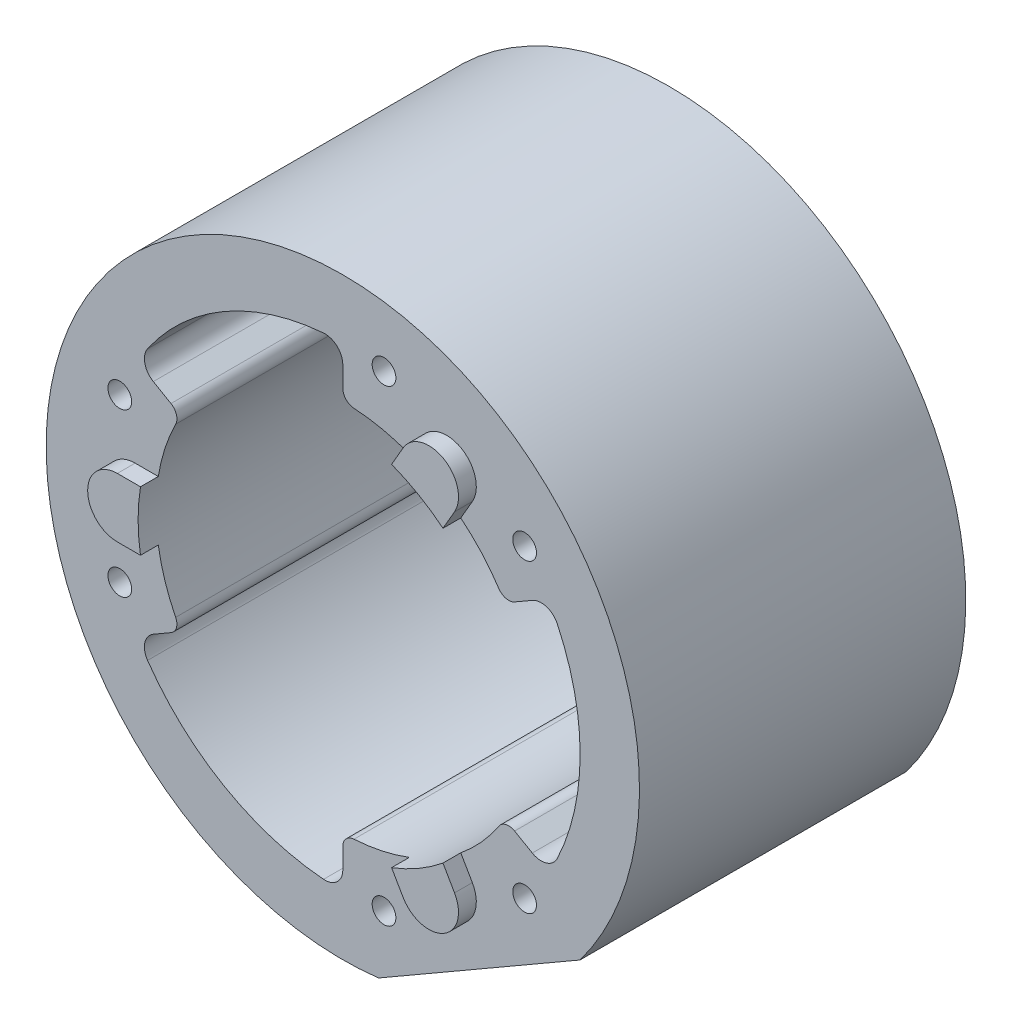
SolidWorks part; units mm, degrees
material "ABS"
ref_plane "Front Plane" through (0, 0, 0) normal (0, 0, 1) x (1, 0, 0)
ref_plane "Top Plane" through (0, 0, 0) normal (0, 1, 0) x (1, 0, 0)
ref_plane "Right Plane" through (0, 0, 0) normal (1, 0, 0) x (0, 0, -1)
sketch "Sketch1" plane through (0, 0, 0) normal (0, 0, 1) x (1, 0, 0)
  line L2 (-28.9601, 16.7201) -> (-31.9374, 18.4391)
  line L3 (0, 33.4402) -> (0, 36.8782)
  line L6 (28.9601, 16.7201) -> (31.9374, 18.4391)
  line L7 (28.9601, -16.7201) -> (31.9374, -18.4391)
  line L10 (0, -33.4402) -> (0, -36.8782)
  line L11 (-28.9601, -16.7201) -> (-31.9374, -18.4391)
  arc A0 (39.9706, -30.0392) -> (6.0294, -49.6351) centre (0, 0) ccw
  circle A1 centre (-37.5877, 13.6808) radius 2
  circle A2 centre (-37.5877, -13.6808) radius 2
  arc A3 (26.2908, 17.3506) -> (1.8806, 31.4438) centre (0, 0) ccw
  arc A4 (-28.1714, 14.0933) -> (-28.9601, 16.7201) centre (-29.9601, 14.9881) ccw
  arc A5 (-32.9053, 22.7429) -> (-31.9374, 18.4391) centre (-30.4374, 21.0372) ccw
  arc A6 (-3.2432, 39.8683) -> (-32.9053, 22.7429) centre (0, 0) ccw
  arc A7 (0, 36.8782) -> (-3.2432, 39.8683) centre (-3, 36.8782) ccw
  circle A8 centre (6.9459, 39.3923) radius 2
  arc A9 (1.8806, -31.4438) -> (26.2908, -17.3506) centre (0, 0) ccw
  circle A10 centre (30.6418, 25.7115) radius 2
  arc A11 (26.2908, 17.3506) -> (28.9601, 16.7201) centre (27.9601, 18.4522) ccw
  arc A12 (36.1486, 17.1254) -> (31.9374, 18.4391) centre (33.4374, 15.841) ccw
  arc A13 (36.1486, -17.1254) -> (36.1486, 17.1254) centre (0, 0) ccw
  arc A14 (31.9374, -18.4391) -> (36.1486, -17.1254) centre (33.4374, -15.841) ccw
  arc A15 (28.9601, -16.7201) -> (26.2908, -17.3506) centre (27.9601, -18.4522) ccw
  circle A16 centre (30.6418, -25.7115) radius 2
  circle A18 centre (6.9459, -39.3923) radius 2
  arc A19 (1.8806, -31.4438) -> (26.2908, -17.3506) centre (0, 0) ccw
  arc A20 (1.8806, -31.4438) -> (0, -33.4402) centre (2, -33.4402) ccw
  arc A21 (-3.2432, -39.8683) -> (0, -36.8782) centre (-3, -36.8782) ccw
  arc A22 (-32.9053, -22.7429) -> (-3.2432, -39.8683) centre (0, 0) ccw
  arc A23 (-31.9374, -18.4391) -> (-32.9053, -22.7429) centre (-30.4374, -21.0372) ccw
  arc A24 (-28.9601, -16.7201) -> (-28.1714, -14.0933) centre (-29.9601, -14.9881) ccw
  arc A26 (0, 33.4402) -> (1.8806, 31.4438) centre (2, 33.4402) ccw
  arc A27 (26.2908, 17.3506) -> (1.8806, 31.4438) centre (0, 0) ccw
  arc A28 (-28.1714, 14.0933) -> (-28.1714, -14.0933) centre (0, 0) ccw
  circle A30 centre (0, 0) radius 50
extrude "Boss-Extrude1" add sketch "Sketch1" along normal blind 55 contours A0 A30 A1 A2 A8 A10 A16 A18 A28 A4 L2 A5 A6 A7 L3 A26 A3 A11 L6 A12 A13 A14 L7 A15 A9 A20 L10 A21 A22 A23 L11 A24 region at (24.2929, -42.0765, 0)
sketch "Sketch2" plane through (0, 0, 55) normal (0, 0, 1) x (1, 0, 0)
  line L0 (-35, -5) -> (-31.1006, -5)
  line L1 (-35, 5) -> (-31.1006, 5)
  line L2 (21.8301, 27.8109) -> (19.8804, 24.4339)
  line L3 (13.1699, 32.8109) -> (11.2202, 29.4339)
  line L4 (21.8301, -27.8109) -> (19.8804, -24.4339)
  line L6 (13.1699, -32.8109) -> (11.2202, -29.4339)
  arc A0 (-35, 5) -> (-35, -5) centre (-35, 0) ccw
  arc A1 (21.8301, 27.8109) -> (13.1699, 32.8109) centre (17.5, 30.3109) ccw
  arc A2 (13.1699, -32.8109) -> (21.8301, -27.8109) centre (17.5, -30.3109) ccw
  arc A5 (-31.1006, 5) -> (-31.1006, -5) centre (0, 0) ccw
  arc A6 (11.2202, -29.4339) -> (19.8804, -24.4339) centre (0, 0) ccw
  arc A7 (19.8804, 24.4339) -> (11.2202, 29.4339) centre (0, 0) ccw
extrude "Boss-Extrude2" add sketch "Sketch2" along normal blind 3
sketch "Sketch3" plane through (0, 0, 55) normal (0, 0, 1) x (1, 0, 0)
  line L0 (6.0294, -49.6351) -> (39.9706, -30.0392)
  arc A1 (6.0294, -49.6351) -> (39.9706, -30.0392) centre (0, 0) ccw
extrude "Cut-Extrude1" cut sketch "Sketch3" against normal through all
sketch "Sketch4" plane through (23, -39.8372, 0) normal (0.5, -0.866, 0) x (0.866, 0.5, 0)
  line L0 (-19.5959, 27.5) -> (19.5959, 27.5) construction
  line L1 (-19.5959, 0) -> (-19.5959, 55) construction
  line L2 (19.5959, 0) -> (19.5959, 55) construction
  line L3 (0, 55) -> (0, 0) construction
  line L4 (19.5959, 55) -> (-19.5959, 55) construction
  circle A0 centre (0, 41.5) radius 2.6
  circle A1 centre (0, 13.5) radius 2.6
  dimension "D1" = 5.2
  dimension "D2" = 5.2
  dimension "D3" = 14
  dimension "D4" = 14
extrude "Cut-Extrude2" cut sketch "Sketch4" against normal up to next
extrude "Boss-Extrude3" add sketch "Sketch2<2>" along normal blind 3 and the other way blind 58
sketch "Sketch2<2>" plane through (0, 0, 55) normal (0, 0, 1) x (1, 0, 0) same geometry as "Sketch2"
